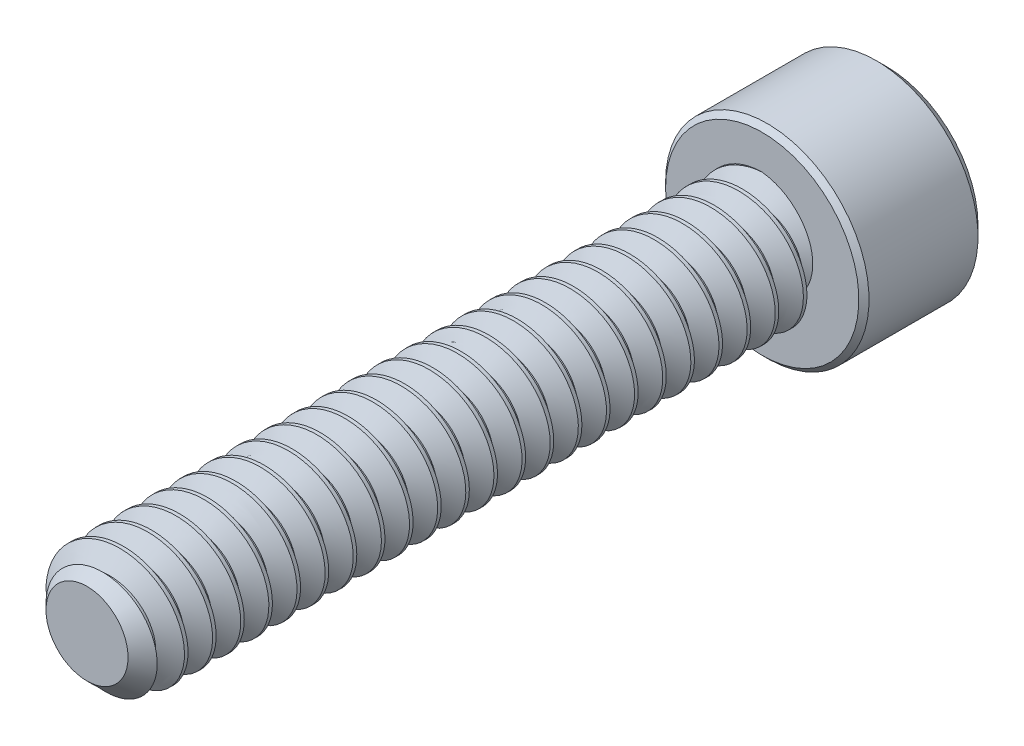
SolidWorks part; units mm, degrees
ref_plane "Front Plane" through (0, 0, 0) normal (0, 0, 1) x (1, 0, 0)
ref_plane "Top Plane" through (0, 0, 0) normal (0, 1, 0) x (1, 0, 0)
ref_plane "Right Plane" through (0, 0, 0) normal (1, 0, 0) x (0, 0, -1)
sketch "Sketch0" plane through (0, 0, 0) normal (1, 0, 0) x (0, 0, -1)
  line L0 (0, 0) -> (19.05, 0) construction
  point P2 (22.5552, 0)
  point P4 (0, 0)
  dimension "D1" = 19.05
  dimension "D2" = 3.5052
  dimension "Min Thread" = 0
sketch "Sketch1" plane through (0, 0, 0) normal (0, 0, 1) x (1, 0, 0)
  circle A0 centre (0, 0) radius 1.7526
  dimension "OD" = 3.5052
extrude "Extrude1" add sketch "Sketch1" against normal blind 19.05
sketch "Sketch2" plane through (0, 0, 0) normal (0, 0, 1) x (1, 0, 0)
  circle A0 centre (0, 0) radius 1.7526 construction
  circle A1 centre (0, 0) radius 1.7526
curve "Helix/Spiral1" pitch 0.7937 height 19.8438 turns 25 parameters "pitch"=0.7937
chamfer "Chamfer3" distance 0.5953 angle 45 1 edges at (1.7526, 0, 0)
sketch "Sketch3" plane through (0, 0, 0) normal (1, 0, 0) x (0, 0, -1)
  line L0 (-0.6945, 1.7526) -> (-0.3969, 1.237)
  line L1 (-0.3969, 1.237) -> (-0.2977, 1.237)
  line L2 (-0.2977, 1.237) -> (0, 1.7526)
  line L3 (-0.6945, 1.7526) -> (0, 1.7526)
  line L4 (-0.3473, 1.7526) -> (-0.3473, 1.237) construction
  line L5 (-0.5457, 1.4948) -> (-0.1488, 1.4948) construction
  line L6 (0, 1.7526) -> (0, -1.7526) construction
  dimension "D1" = 0.0992
  dimension "D2" = 0.3969
  dimension "D3" = 60
sweep "Cut-Sweep1" cut profiles "Sketch3" path "Helix/Spiral1"
sketch "Sketch5" plane through (0, 0, 0) normal (1, 0, 0) x (0, 0, -1)
  line L0 (19.05, -1.2539) -> (19.05, 1.2505) construction
  line L1 (19.05, 1.7526) -> (0, 1.7526)
  line L2 (19.05, 1.7526) -> (19.05, 0)
  line L3 (19.05, 0) -> (-0.6379, 0)
  line L4 (0, 0) -> (19.05, 0) construction
  line L5 (0, 1.7526) -> (-0.6379, 0)
  line L6 (0, 0) -> (21.59, 0) construction
  dimension "D1" = 70
  dimension "D3" = 2.54
revolve "partially thread" [suppressed] add sketch "Sketch5" angle 360 about L6
sketch "Sketch6" plane through (0, 0, -19.05) normal (0, 0, -1) x (-1, 0, 0)
  circle A0 centre (0, 0) radius 2.8702
  dimension "head dia" = 5.7404
extrude "Extrude2" add sketch "Sketch6" along normal blind 3.5052
sketch "Sketch7" plane through (0, 0, -22.5552) normal (0, 0, -1) x (-1, 0, 0)
  line L1 (0, 1.604) -> (-1.3891, 0.802)
  line L2 (-1.3891, 0.802) -> (-1.3891, -0.802)
  line L3 (-1.3891, -0.802) -> (0, -1.604)
  line L4 (0, -1.604) -> (1.3891, -0.802)
  line L5 (1.3891, -0.802) -> (1.3891, 0.802)
  line L6 (1.3891, 0.802) -> (0, 1.604)
  circle A0 centre (0, 0) radius 1.3891 construction
  dimension "hex dia" = 2.7781
extrude "Cut-Extrude1" cut sketch "Sketch7" against normal blind 2.0836
sketch "Sketch8" plane through (0, 0, -22.5552) normal (0, 0, -1) x (-1, 0, 0)
  circle A0 centre (0, 0) radius 1.604
extrude "Cut-Extrude2" cut sketch "Sketch8" against normal through all draft 45
chamfer "Chamfer1" distance 0.287 angle 45 1 edges at (-2.8702, 0, -22.5552)
chamfer "Chamfer2" distance 0.1435 angle 45 1 edges at (-2.8702, 0, -19.05)
sketch "Sketch9" plane through (0, 0, 0) normal (1, 0, 0) x (0, 0, -1)
  line L0 (0, 1.7526) -> (0, -1.7526) construction
  line L1 (1.9844, 1.7526) -> (1.9844, -1.7526) construction
  line L2 (22.5552, 2.8702) -> (22.5552, -2.8702) construction
  line L3 (19.05, 2.8702) -> (19.05, -2.8702) construction
  line L4 (19.05, 2.7267) -> (19.05, -2.7267) construction
  line L5 (22.5552, -2.5832) -> (22.5552, 2.5832) construction
  line L6 (19.05, -2.8702) -> (19.05, 2.8702) construction
  line L7 (0, 1.1573) -> (0, -1.1573) construction
  line L8 (-0.6945, 1.7526) -> (0, 1.7526) construction
  line L9 (1.9844, 0) -> (0, 0) construction
  dimension "D1" = 1.9844
equation "\"D3@Helix/Spiral1\" = \"screw length@Extrude1\"+\"pitch@Helix/Spiral1\""
equation "\"D1@Sketch3\" = \"pitch@Helix/Spiral1\"*.125"
equation "\"D2@Sketch3\" = \"pitch@Helix/Spiral1\"*.5"
equation "\"D1@Cut-Extrude1\" = \"hex dia@Sketch7\"*.75"
equation "\"D1@Chamfer1\" = \"head dia@Sketch6\"*.05"
equation "\"D1@Sketch9\" = \"pitch@Helix/Spiral1\"*2.50"
equation "\"D1@Chamfer2\" = \"D1@Chamfer1\"/2"
equation "\"D1@Chamfer3\" = \"pitch@Helix/Spiral1\"*.750"
equation "\"D1@Sketch0\" = \"screw length@Extrude1\""
equation "\"D2@Sketch0\" = \"head depth@Extrude2\""
